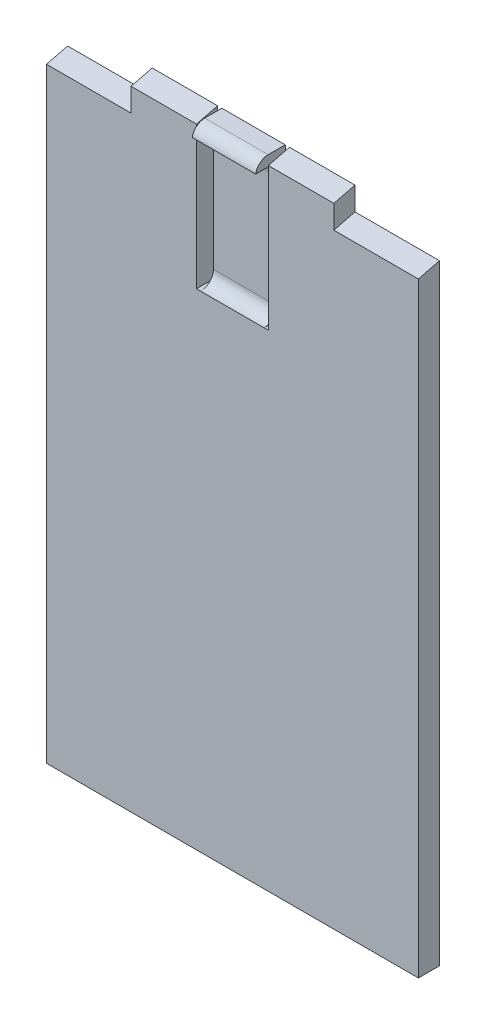
SolidWorks part; units mm, degrees
material "ABS"
ref_plane "Front Plane" through (0, 0, 0) normal (0, 0, 1) x (1, 0, 0)
ref_plane "Top Plane" through (0, 0, 0) normal (0, 1, 0) x (1, 0, 0)
ref_plane "Right Plane" through (0, 0, 0) normal (1, 0, 0) x (0, 0, -1)
sketch "Sketch1" plane through (0, 0, 0) normal (0, 0, 1) x (1, 0, 0)
  line L0 (0, 0) -> (0, 144.5)
  line L1 (0, 144.5) -> (20, 144.5)
  line L2 (20, 144.5) -> (20, 150)
  line L3 (20, 150) -> (35.5, 150)
  line L4 (35.5, 150) -> (35.5, 115)
  line L5 (35.5, 115) -> (36.5, 115)
  line L6 (36.5, 115) -> (36.5, 150)
  line L7 (36.5, 150) -> (51.5, 150)
  line L8 (51.5, 150) -> (51.5, 115)
  line L9 (51.5, 115) -> (52.5, 115)
  line L10 (52.5, 115) -> (52.5, 150)
  line L11 (52.5, 150) -> (68, 150)
  line L12 (68, 150) -> (68, 144.5)
  line L13 (68, 144.5) -> (88, 144.5)
  line L14 (88, 144.5) -> (88, 0)
  line L15 (88, 0) -> (0, 0)
  dimension "D1" = 144.5
  dimension "D2" = 20
  dimension "D3" = 15.5
  dimension "D4" = 1
  dimension "D5" = 35
  dimension "D6" = 15
  dimension "D7" = 1
  dimension "D8" = 15.5
  dimension "D9" = 5.5
  dimension "D11" = 20
extrude "Boss-Extrude1" add sketch "Sketch1" along normal blind 5
sketch "Sketch2" plane through (88, 0, 0) normal (1, 0, 0) x (0, 0, -1)
  line L4 (-5, 144.5) -> (0, 144.5)
  line L8 (0, 144.5) -> (-5, 143.2534)
  line L9 (-5, 0) -> (-5, 144.5) construction
  line L10 (-5, 143.2534) -> (-5, 144.5)
  dimension "D1" = 104
extrude "Cut-Extrude1" cut sketch "Sketch2" against normal blind 20
sketch "Sketch3" plane through (0, 0, 0) normal (-1, 0, 0) x (0, 0, 1)
  line L0 (5, 144.5) -> (0, 144.5)
  line L7 (5, 144.5) -> (5, 143.2534)
  line L8 (5, 144.5) -> (5, 0) construction
  line L9 (5, 143.2534) -> (0, 144.5)
  dimension "D1" = 104
extrude "Cut-Extrude2" cut sketch "Sketch3" against normal blind 20
sketch "Sketch4" plane through (68, 0, 0) normal (1, 0, 0) x (0, 0, -1)
  line L0 (0, 150) -> (-5, 148.7534)
  line L1 (-5, 143.2534) -> (-5, 150) construction
  line L2 (-5, 148.7534) -> (-5, 150)
  line L3 (-5, 150) -> (0, 150)
  dimension "D1" = 104
extrude "Cut-Extrude3" cut sketch "Sketch4" against normal blind 15.5
sketch "Sketch5" plane through (20, 0, 0) normal (-1, 0, 0) x (0, 0, 1)
  line L0 (0, 150) -> (5, 150)
  line L1 (5, 150) -> (0, 150) construction
  line L2 (5, 150) -> (5, 143.2534) construction
  line L3 (5, 150) -> (5, 148.7534)
  line L4 (5, 148.7534) -> (0, 150)
  dimension "D1" = 104
extrude "Cut-Extrude4" cut sketch "Sketch5" against normal blind 15.5
sketch "Sketch6" plane through (0, 0, 5) normal (0, 0, 1) x (1, 0, 0)
  line L0 (36.5, 147.5) -> (51.5, 147.5)
  line L1 (36.5, 150) -> (36.5, 115) construction
  line L2 (51.5, 115) -> (51.5, 150) construction
  line L3 (51.5, 147.5) -> (51.5, 115)
  line L4 (51.5, 115) -> (36.5, 115)
  line L5 (36.5, 115) -> (36.5, 147.5)
  line L6 (51.5, 150) -> (36.5, 150) construction
  dimension "D1" = 2.5
extrude "Cut-Extrude5" cut sketch "Sketch6" against normal blind 3
fillet "Fillet1" radius 3 1 edges at (44, 115, 2)
sketch "Sketch7" plane through (0, 0, 5) normal (0, 0, 1) x (1, 0, 0)
  line L0 (36.5, 147.5) -> (51.5, 147.5)
  line L1 (51.5, 147.5) -> (51.5, 150)
  line L2 (51.5, 150) -> (36.5, 150)
  line L3 (36.5, 150) -> (36.5, 147.5)
extrude "Boss-Extrude2" add sketch "Sketch7" along normal blind 2
fillet "Fillet2" radius 3 1 edges at (44, 147.5, 2)
fillet "Fillet3" radius 3 1 edges at (44, 150, 7)
